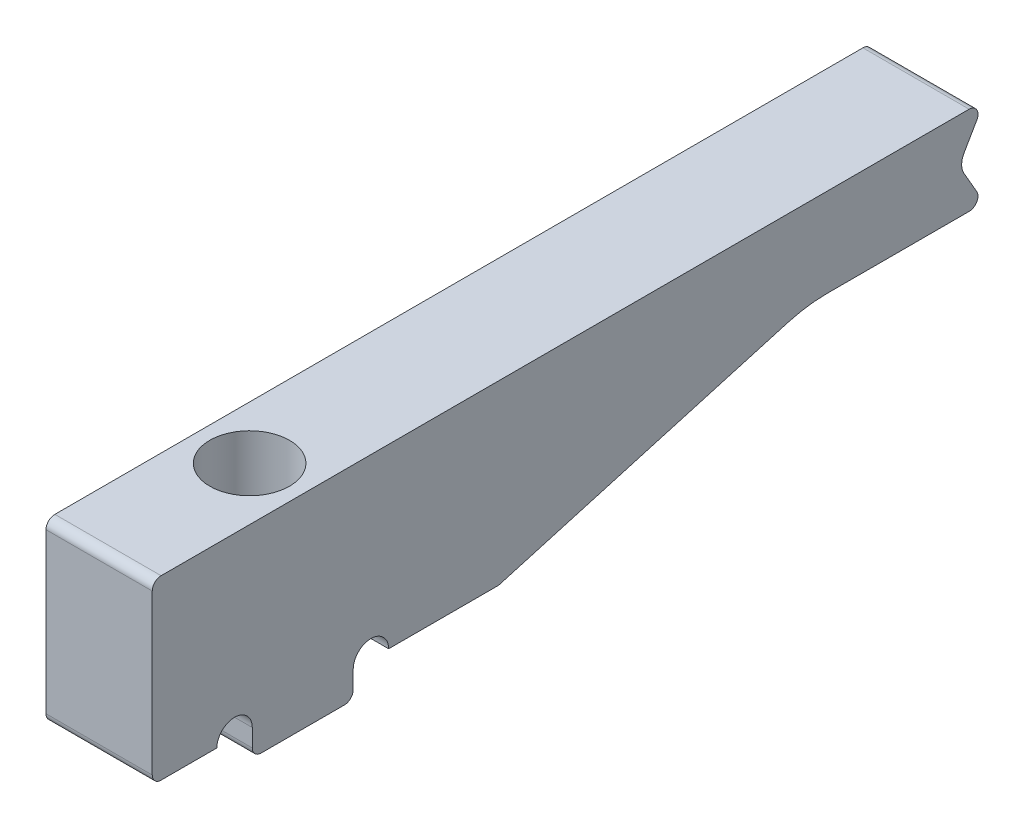
SolidWorks part; units mm, degrees
ref_plane "Plan de face" through (0, 0, 0) normal (0, 0, 1) x (1, 0, 0)
ref_plane "Plan de dessus" through (0, 0, 0) normal (0, 1, 0) x (1, 0, 0)
ref_plane "Plan de droite" through (0, 0, 0) normal (1, 0, 0) x (0, 0, -1)
sketch "Esquisse1" plane through (0, 0, 0) normal (0, 0, 1) x (1, 0, 0)
  line L1 (-3, -2.5) -> (3, -2.5)
  line L2 (-3, -2.5) -> (-3, 2.5)
  line L3 (-3, 2.5) -> (3, 2.5)
  line L4 (3, -2.5) -> (3, 2.5)
  line L5 (-3, -2.5) -> (3, 2.5) construction
  line L6 (-3, 2.5) -> (3, -2.5) construction
  point P0 (0, 0)
  dimension "D1" = 5
  dimension "D2" = 6
extrude "Boss.-Extru.1" add sketch "Esquisse1" along normal mid plane 17
sketch "Esquisse5" plane through (-2.5, 0, -8.5) normal (0, 0, 1) x (1, 0, 0)
  line L0 (5.8, 0) -> (-0.8, 0) construction
  line L1 (-0.5, -2.5) -> (5.5, -2.5)
  line L2 (-0.5, -2.5) -> (-0.5, 2.5)
  line L3 (-0.5, 2.5) -> (5.5, 2.5)
  line L4 (5.5, -2.5) -> (5.5, 2.5)
  line L5 (-0.5, -2.5) -> (5.5, 2.5) construction
  line L6 (-0.5, 2.5) -> (5.5, -2.5) construction
  line L11 (2.5, -5.225) -> (2.5, 5.225) construction
  line L12 (5.5, 2.5) -> (-0.5, 2.5) construction
  point P0 (2.5, 0)
  dimension "D1" = 6
extrude "Boss.-Extru.3" add sketch "Esquisse5" against normal blind 30
sketch "Esquisse6" plane through (3, 0, 0) normal (1, 0, 0) x (0, 0, -1)
  line L0 (38.5, 2.5) -> (37.0566, 0)
  line L1 (3.3, 0) -> (-3.3, 0) construction
  line L2 (37.0566, 0) -> (38.5, -2.5)
  line L3 (38.5, -2.5) -> (38.5, 2.5)
  dimension "D1" = 120
extrude "Enlèv. mat.-Extru.2" cut sketch "Esquisse6" against normal through all
sketch "Esquisse7" plane through (0, -2.5, 0) normal (0, -1, 0) x (1, 0, 0)
  line L0 (3, 8.5) -> (3, -38.5) construction
  line L1 (-3, 8.5) -> (3, 8.5)
  line L2 (-3, 8.5) -> (-3, -8.5)
  line L3 (-3, -8.5) -> (3, -8.5)
  line L4 (3, 8.5) -> (3, -8.5)
  line L5 (-3, 8.5) -> (-3, -38.5) construction
  line L7 (3, 8.5) -> (-3, -8.5) construction
  point P6 (0, 0)
extrude "Boss.-Extru.4" add sketch "Esquisse7" along normal blind 5
sketch "Esquisse2" plane through (0, 2.5, 0) normal (0, 1, 0) x (1, 0, 0)
  circle A0 centre (0, 0) radius 2.25
  dimension "D1" = 4.5
extrude "Enlèv. mat.-Extru.1" cut sketch "Esquisse2" against normal through all
sketch "Esquisse9" plane through (0, -7.5, 0) normal (0, -1, 0) x (1, 0, 0)
  line L0 (3, -8.5) -> (3, 8.5) construction
  line L1 (-3, -2.85) -> (3, -2.85)
  line L2 (-3, -2.85) -> (-3, 2.85)
  line L3 (-3, 2.85) -> (3, 2.85)
  line L4 (3, -2.85) -> (3, 2.85)
  line L5 (-3, -2.85) -> (3, 2.85) construction
  line L6 (-3, 2.85) -> (3, -2.85) construction
  point P0 (0, 0)
  dimension "D1" = 5.7
extrude "Boss.-Extru.6" add sketch "Esquisse9" along normal blind 1.5
sketch "Esquisse10" plane through (3, 0, 0) normal (1, 0, 0) x (0, 0, -1)
  line L0 (-2.85, -7.5) -> (-8.5, -7.5) construction
  line L1 (-2.85, -9) -> (-2.85, -7.5) construction
  line L2 (-4.85, -7.5) -> (-2.85, -7.5)
  line L3 (0, 3.3) -> (0, -3.3) construction
  line L4 (4.85, -7.5) -> (2.85, -7.5)
  arc A0 (-4.85, -7.5) -> (-2.85, -7.5) centre (-3.85, -7.5) cw
  arc A1 (4.85, -7.5) -> (2.85, -7.5) centre (3.85, -7.5) ccw
  dimension "D1" = 1
extrude "Enlèv. mat.-Extru.3" cut sketch "Esquisse10" against normal through all
chamfer "Chanfrein2" distance 20 angle 16 1 edges at (0, -2.5, -8.5) first distance on face at (0, -2.5, -23.5)
fillet "Congé1" radius 0.5 7 edges at (0, 2.5, 8.5) (0, 2.5, -38.5) (0, -2.5, -38.5) (0, -9, -2.85) (0, -9, 2.85) (0, -7.5, 8.5) (0, -7.5, -11.0629)
fillet "Congé2" radius 1 1 edges at (0, 0, -37.0566)
fillet "Congé3" radius 8 1 edges at (0, -2.5, -28.5)
